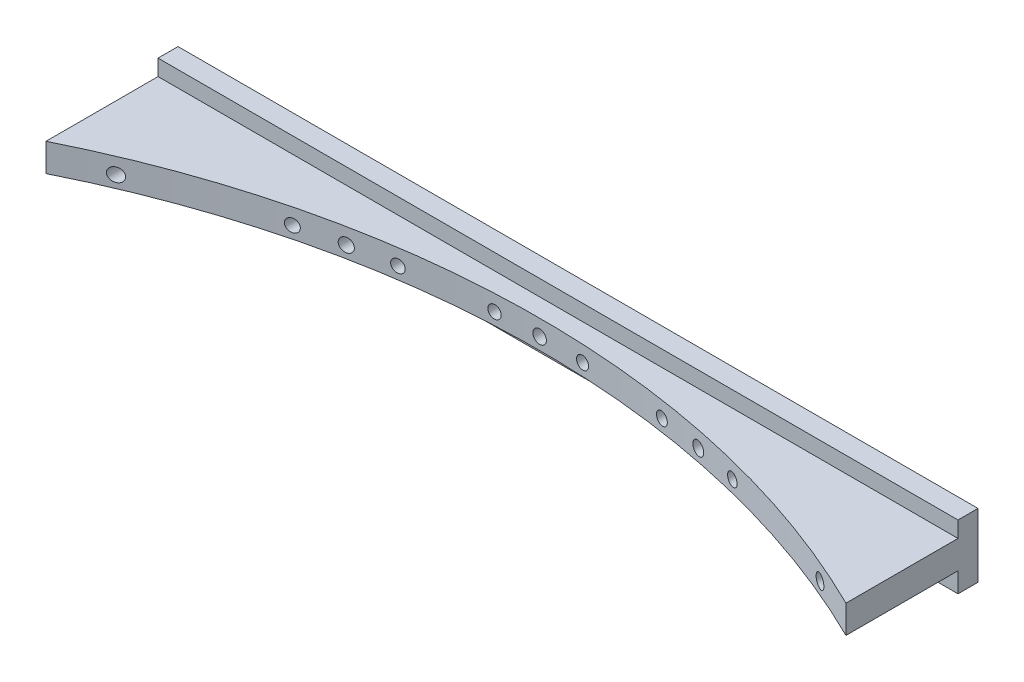
SolidWorks part; units mm, degrees
material "6061-T6 (SS)"
ref_plane "Front" through (0, 0, 0) normal (0, 0, 1) x (1, 0, 0)
ref_plane "Top" through (0, 0, 0) normal (0, 1, 0) x (1, 0, 0)
ref_plane "Right" through (0, 0, 0) normal (1, 0, 0) x (0, 0, -1)
sketch "Sketch1" plane through (0, 0, 0) normal (0, 1, 0) x (1, 0, 0)
  line L1 (0, 0) -> (635, 0)
  line L2 (0, 0) -> (0, 900)
  line L3 (0, 900) -> (635, 900)
  line L4 (635, 0) -> (635, 900)
  dimension "D1" = 635
  dimension "D2" = 900
extrude "Boss-Extrude1" add sketch "Sketch1" along normal blind 50.8
sketch "Sketch2" plane through (0, 50.8, 0) normal (0, 1, 0) x (-1, 0, 0)
  line L0 (-317.5, -900) -> (-317.5, 809.4054) construction
  line L1 (-635, -900) -> (0, -900) construction
  line L2 (-282.5, -855.55) -> (-352.5, -855.55) construction
  line L3 (-352.5, -855.55) -> (-352.5, -154.55) construction
  line L4 (-352.5, -154.55) -> (-282.5, -154.55) construction
  dimension "D1" = 70
  dimension "D2" = 35
  dimension "D3" = 70
  dimension "D4" = 44.45
  dimension "D5" = 701
hole_wizard "3/8 (0.375) Diameter Hole1" positions "Sketch3" profile "Sketch4" hole size "3/8" standard "ANSI Inch" end condition through all
sketch "Sketch3" plane through (0, 50.8, 0) normal (0, 1, 0) x (-1, 0, 0)
  line L0 (-282.5, -855.55) -> (-352.5, -855.55) construction
  point P0 (-317.5, -855.55)
sketch "Sketch4" plane through (317.5, 50.8, -855.55) normal (1, 0, 0) x (0, 0, 1)
  line L0 (0, 0) -> (0, 50.8)
  line L1 (0, 50.8) -> (4.7625, 50.8)
  line L2 (4.7625, 50.8) -> (4.7625, 0)
  line L5 (4.7625, 0) -> (0, 0)
  line L11 (0, -6.35) -> (0, 107.95) construction
  dimension "Thru Hole Dia." = 9.525
  dimension "Thru Hole Depth" = 50.8
hole_wizard "1 (1) Diameter Hole1" positions "Sketch8" profile "Sketch7" hole size "1" standard "ANSI Inch" end condition through all
sketch "Sketch8" plane through (0, 50.8, 0) normal (0, 1, 0) x (1, 0, 0)
  line L0 (352.5, 154.55) -> (282.5, 154.55) construction
  point P0 (317.5, 154.55)
sketch "Sketch7" plane through (317.5, 50.8, -154.55) normal (1, 0, 0) x (0, 0, 1)
  line L0 (0, 0) -> (0, 50.8)
  line L1 (0, 50.8) -> (12.7, 50.8)
  line L2 (12.7, 50.8) -> (12.7, 0)
  line L5 (12.7, 0) -> (0, 0)
  line L11 (0, -6.35) -> (0, 107.95) construction
  dimension "Thru Hole Dia." = 25.4
  dimension "Thru Hole Depth" = 50.8
pattern_circular "CirPattern1" count 60 over 360 about axis through (317.5, 50.8, -154.55) along (0, 1, 0) skipping 5, 6, 7, 8, 9, 10, 11, 12, 13, 14, 15, 16, 17, 18, 19, 20, 21, 22, 23, 24, 25, 26, 27, 28, 29, 30, 31, 32, 33, 34, 35, 36, 37, 38, 39, 40, 41, 42, 43, 44, 45, 46, 47, 48, 49, 50, 51, 52, 53, 54, 55 of "3/8 (0.375) Diameter Hole1"
sketch "Sketch9" plane through (0, 50.8, 0) normal (0, 1, 0) x (1, 0, 0)
  line L0 (352.5, 154.55) -> (282.5, 154.55) construction
  circle A0 centre (317.5, 154.55) radius 715
  dimension "D1" = 1430
extrude "Cut-Extrude1" cut sketch "Sketch9" against normal through all
sketch "Sketch10" plane through (0, 0, -900) normal (0, 0, -1) x (-1, 0, 0)
  line L0 (-317.5, 75.4) -> (-317.5, -24.6) construction
  line L1 (0, 50.8) -> (0, 0) construction
  point P4 (0, 25.4)
  dimension "D1" = 100
  dimension "D2" = 50
  dimension "D3" = 317.5
hole_wizard "CBORE for 3/8 Socket Head Cap Screw1" positions "Sketch11" profile "Sketch12" counterbore size "3/8" standard "ANSI Inch" end condition through all
sketch "Sketch11" plane through (0, 0, -900) normal (0, 0, -1) x (-1, 0, 0)
  line L0 (-635, 50.8) -> (0, 50.8) construction
  line L1 (-317.5, 75.4) -> (-317.5, -24.6) construction
  point P0 (-492.125, 25.4)
  dimension "D1" = 25.4
  dimension "D2" = 174.625
sketch "Sketch12" plane through (492.125, 25.4, -900) normal (1, 0, 0) x (0, 1, 0)
  line L0 (0, 0) -> (0, 104.8107)
  line L1 (0, 104.8107) -> (5.0419, 104.8107)
  line L3 (5.0419, 104.8107) -> (5.0419, 9.525)
  line L4 (5.0419, 9.525) -> (7.9375, 9.525)
  line L5 (7.9375, 9.525) -> (7.9375, 0)
  line L7 (7.9375, 0) -> (0, 0)
  line L11 (0, -6.35) -> (0, 107.95) construction
  dimension "Thru Hole Dia." = 10.0838
  dimension "Thru Hole Depth" = 104.8107
  dimension "C'Bore Dia." = 15.875
  dimension "C'Bore Depth" = 9.525
fillet "Fillet1" radius 0.5 1 edges at (487.0831, 25.4, -890.475)
pattern_linear "LPattern1" count 6 spacing 69.85 along (-1, 0, 0) of "CBORE for 3/8 Socket Head Cap Screw1", "Fillet1"
hole_wizard "1/2-13 Tapped Hole1" positions "Sketch13" profile "Sketch14" tap size "1/2-13" standard "ANSI Inch" end condition through all
sketch "Sketch13" plane through (0, 0, -900) normal (0, 0, -1) x (-1, 0, 0)
  line L0 (-635, 50.8) -> (0, 50.8) construction
  line L1 (-317.5, 75.4) -> (-317.5, -24.6) construction
  point P0 (-596.9, 25.4)
  dimension "D1" = 25.4
  dimension "D2" = 279.4
sketch "Sketch14" plane through (596.9, 25.4, -900) normal (1, 0, 0) x (0, 1, 0)
  line L0 (0, 0) -> (0, 104.8107)
  line L1 (0, 104.8107) -> (5.3581, 104.8107)
  line L2 (5.3581, 104.8107) -> (5.3581, 0)
  line L5 (5.3581, 0) -> (0, 0)
  line L11 (0, -6.35) -> (0, 107.95) construction
  dimension "Thru Tap Drill Dia." = 10.7163
  dimension "Thru Tap Drill Depth" = 104.8107
cosmetic thread "Hole Thread1" parameters "D2"=12.7
pattern_linear "LPattern2" count 5 spacing 139.7 along (-1, 0, 0) of "1/2-13 Tapped Hole1"
cosmetic thread "Hole Thread2" parameters "D2"=12.7
cosmetic thread "Hole Thread3" parameters "D2"=12.7
cosmetic thread "Hole Thread4" parameters "D2"=12.7
cosmetic thread "Hole Thread5" parameters "D2"=12.7
cosmetic thread "Hole Thread6" parameters "D2"=12.7
cosmetic thread "Hole Thread7" parameters "D2"=12.7
cosmetic thread "Hole Thread8" parameters "D2"=12.7
cosmetic thread "Hole Thread9" parameters "D2"=12.7
sketch "Sketch19" plane through (0, 0, 0) normal (0, -1, 0) x (1, 0, 0)
  line L0 (0, -900) -> (0, -795.1893) construction
  line L1 (0, -884.125) -> (635, -884.125)
  line L2 (0, -884.125) -> (0, -784.125)
  line L3 (0, -784.125) -> (635, -784.125)
  line L4 (635, -884.125) -> (635, -784.125)
  line L5 (635, -795.1893) -> (635, -900) construction
  line L6 (635, -900) -> (0, -900) construction
  dimension "D1" = 0
  dimension "D2" = 0
  dimension "D3" = 15.875
  dimension "D4" = 100
extrude "Cut-Extrude2" cut sketch "Sketch19" against normal blind 15.875
sketch "Sketch20" plane through (0, 50.8, 0) normal (0, 1, 0) x (1, 0, 0)
  line L0 (0, 900) -> (0, 795.1893) construction
  line L1 (0, 784.125) -> (635, 784.125)
  line L2 (0, 784.125) -> (0, 884.125)
  line L3 (0, 884.125) -> (635, 884.125)
  line L4 (635, 784.125) -> (635, 884.125)
  line L5 (635, 795.1893) -> (635, 900) construction
  line L6 (635, 900) -> (0, 900) construction
  dimension "D1" = 0
  dimension "D2" = 0
  dimension "D3" = 15.875
  dimension "D4" = 100
extrude "Cut-Extrude3" cut sketch "Sketch20" against normal blind 12.7
ref_axis "Axis1" through (282.575, 25.4, -868.1469) along (0, 0, -1)
ref_axis "Axis2" through (352.425, 25.4, -868.1485) along (0, 0, -1)
